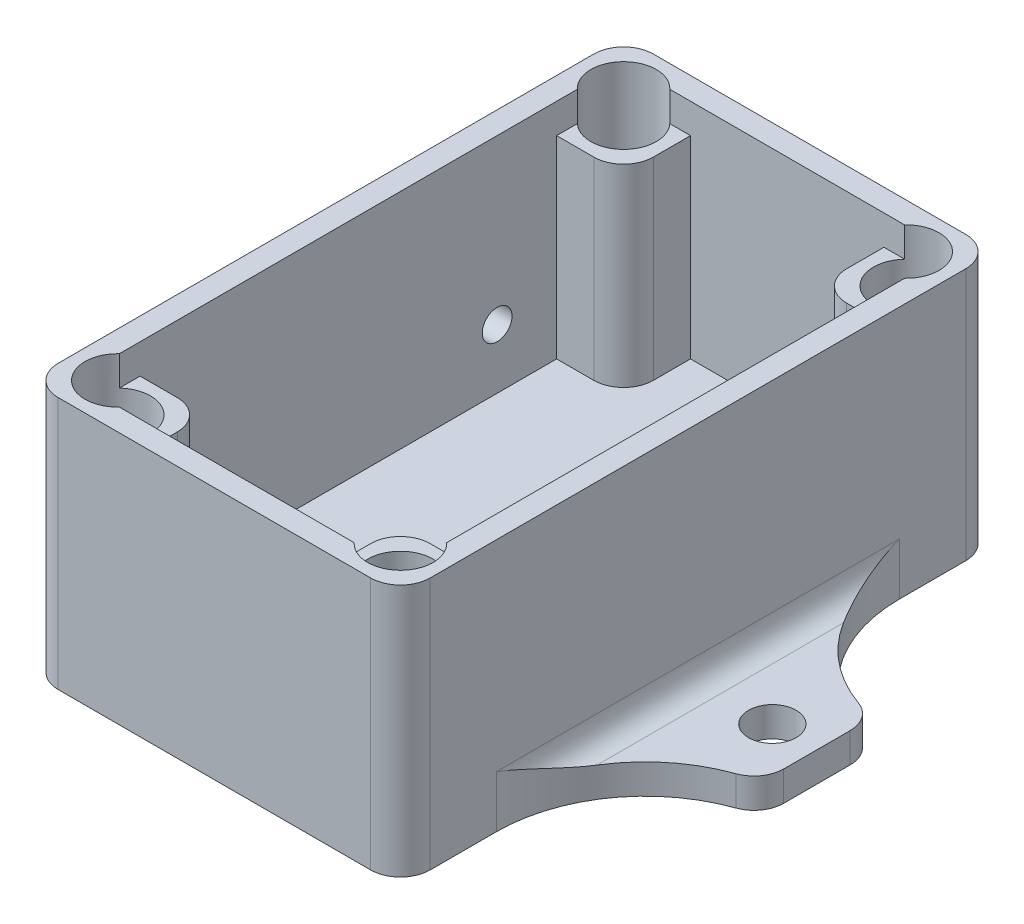
SolidWorks part; units mm, degrees
material "ABS"
ref_plane "Plan de face" through (0, 0, 0) normal (0, 0, 1) x (1, 0, 0)
ref_plane "Plan de dessus" through (0, 0, 0) normal (0, 1, 0) x (1, 0, 0)
ref_plane "Plan de droite" through (0, 0, 0) normal (1, 0, 0) x (0, 0, -1)
sketch "Esquisse1" plane through (0, 0, 0) normal (0, 1, 0) x (1, 0, 0)
  line L1 (-10.5, 20) -> (10.5, 20)
  line L2 (-12.5, 18) -> (-12.5, -18)
  line L3 (-10.5, -20) -> (10.5, -20)
  line L4 (12.5, 18) -> (12.5, -18)
  line L5 (-12.5, 20) -> (12.5, -20) construction
  line L6 (-12.5, -20) -> (12.5, 20) construction
  arc A0 (-12.5, -18) -> (-10.5, -20) centre (-10.5, -18) ccw
  arc A1 (10.5, -20) -> (12.5, -18) centre (10.5, -18) ccw
  arc A2 (10.5, 20) -> (12.5, 18) centre (10.5, 18) cw
  arc A3 (-10.5, 20) -> (-12.5, 18) centre (-10.5, 18) ccw
  point P0 (0, 0)
  dimension "D3" = 2
  dimension "D1" = 25
  dimension "D2" = 40
extrude "Base" add sketch "Esquisse1" along normal blind 2
sketch "Esquisse2" plane through (0, 2, 0) normal (0, 1, 0) x (1, 0, 0)
  line L9 (-10.5, -18.5) -> (10.5, -18.5)
  line L10 (11, -18) -> (11, 18)
  line L11 (10.5, 18.5) -> (-10.5, 18.5)
  line L12 (-11, 18) -> (-11, -18)
  line L13 (-10.5, -18.5) -> (10.5, -18.5)
  line L14 (11, -18) -> (11, 18)
  line L15 (10.5, 18.5) -> (-10.5, 18.5)
  line L16 (-11, 18) -> (-11, -18)
  arc A8 (-11, -18) -> (-10.5, -18.5) centre (-10.5, -18) ccw
  arc A9 (10.5, -18.5) -> (11, -18) centre (10.5, -18) ccw
  arc A10 (11, 18) -> (10.5, 18.5) centre (10.5, 18) ccw
  arc A11 (-10.5, 18.5) -> (-11, 18) centre (-10.5, 18) ccw
  arc A12 (-11, -18) -> (-10.5, -18.5) centre (-10.5, -18) ccw
  arc A13 (10.5, -18.5) -> (11, -18) centre (10.5, -18) ccw
  arc A14 (11, 18) -> (10.5, 18.5) centre (10.5, 18) ccw
  arc A15 (-10.5, 18.5) -> (-11, 18) centre (-10.5, 18) ccw
  arc M9 (-12.5, -18) -> (-10.5, -20) centre (-10.5, -18) ccw
  line M10 (-10.5, -20) -> (10.5, -20)
  arc M11 (10.5, -20) -> (12.5, -18) centre (10.5, -18) ccw
  line M12 (12.5, -18) -> (12.5, 18)
  arc M13 (12.5, 18) -> (10.5, 20) centre (10.5, 18) ccw
  line M14 (10.5, 20) -> (-10.5, 20)
  arc M15 (-10.5, 20) -> (-12.5, 18) centre (-10.5, 18) ccw
  line M16 (-12.5, 18) -> (-12.5, -18)
  dimension "D1" = 1.5
extrude "Mur" add sketch "Esquisse2" along normal blind 15 contours A15 L15 A14 L14 A13 L13 A12 L16 M16 M9 M10 M11 M12 M13 M14 M15 region at (-12.0283, 2, 0)
sketch "Esquisse3" plane through (0, 2, 0) normal (0, 1, 0) x (1, 0, 0)
  line L1 (-11, 18.5) -> (-6.5, 18.5)
  line L2 (-11, 18.5) -> (-11, 14)
  line L3 (-11, 14) -> (-6.5, 14)
  line L4 (-6.5, 18.5) -> (-6.5, 14)
  line L5 (10.5, 18.5) -> (-10.5, 18.5) construction
  line L6 (-11, 18) -> (-11, -18) construction
  line L7 (0, -55) -> (0, 55) construction
  line L8 (11, 14) -> (6.5, 14)
  line L9 (6.5, 18.5) -> (6.5, 14)
  line L10 (11, 18.5) -> (6.5, 18.5)
  line L11 (11, 18.5) -> (11, 14)
  line L12 (-55, 0) -> (55, 0) construction
  line L13 (11, -18.5) -> (11, -14)
  line L14 (11, -18.5) -> (6.5, -18.5)
  line L15 (6.5, -18.5) -> (6.5, -14)
  line L16 (11, -14) -> (6.5, -14)
  line L17 (-11, -14) -> (-6.5, -14)
  line L18 (-6.5, -18.5) -> (-6.5, -14)
  line L19 (-11, -18.5) -> (-6.5, -18.5)
  line L20 (-11, -18.5) -> (-11, -14)
  dimension "D1" = 4.5
extrude "Fixation Vis" add sketch "Esquisse3" along normal blind 13
sketch "Esquisse4" plane through (0, 15, 0) normal (0, 1, 0) x (1, 0, 0)
  line L8 (10.5, 20) -> (-10.5, 20) construction
  line L9 (-6.5, 14) -> (-12.5, 14) construction
  line L10 (-6.5, 14) -> (-6.5, 20) construction
  line L11 (-6.5, 20) -> (-12.5, 20) construction
  line L12 (-12.5, 14) -> (-12.5, 20) construction
  line L13 (-12.5, 18) -> (-12.5, -18) construction
  line L14 (0, -55) -> (0, 55) construction
  line L15 (-55, 0) -> (55, 0) construction
  circle A0 centre (-9.5, 17) radius 2.2
  circle A1 centre (9.5, 17) radius 2.2
  circle A2 centre (9.5, -17) radius 2.2
  circle A3 centre (-9.5, -17) radius 2.2
  point P21 (-9.5, 20)
  point P24 (-12.5, 17)
  dimension "D1" = 4.4
fillet "Congé1" radius 2 4 edges at (-6.5, 8.5, 14) (6.5, 8.5, 14) (6.5, 8.5, -14) (-6.5, 8.5, -14)
extrude "Insert M3" cut sketch "Esquisse4" against normal blind 6 and the other way up to next
sketch "Esquisse5" plane through (-12.5, 0, 0) normal (-1, 0, 0) x (0, 0, 1)
  line L0 (-18, 0) -> (18, 0) construction
  line L1 (-18, 17) -> (-18, 0) construction
  circle A0 centre (-10, 6) radius 1
  dimension "D1" = 2
  dimension "D2" = 6
  dimension "D3" = 8
extrude "Passe-Cable" cut sketch "Esquisse5" against normal up to next
sketch "Esquisse8" plane through (0, 0, 0) normal (0, 1, 0) x (1, 0, 0)
  line L0 (12.5, -18) -> (12.5, 18) construction
  line L1 (12.5, 3.75) -> (20.5, 3.75)
  line L2 (12.5, 3.75) -> (12.5, -3.75)
  line L3 (12.5, -3.75) -> (20.5, -3.75)
  line L4 (20.5, 3.75) -> (20.5, -3.75)
  line L5 (-12.5, 18) -> (-12.5, -18) construction
  line L6 (-12.5, -3.75) -> (-20.5, -3.75)
  line L7 (-12.5, -3.75) -> (-12.5, 3.75)
  line L8 (-12.5, 3.75) -> (-20.5, 3.75)
  line L9 (-20.5, -3.75) -> (-20.5, 3.75)
  point P12 (-20.5, 0)
  point P14 (20.5, 0)
  dimension "D1" = 8
  dimension "D2" = 7.5
extrude "Pates fixation" add sketch "Esquisse8" along normal blind 2
sketch "Esquisse9" plane through (0, 2, 0) normal (0, 1, 0) x (1, 0, 0)
  circle A0 centre (-17.5, 0) radius 1.6
  circle A1 centre (17.5, 0) radius 1.6
  dimension "D2" = 3.2
  dimension "D1" = 35
  dimension "D3" = 17.5
extrude "Passage_Vis" cut sketch "Esquisse9" against normal up to next
fillet "Congé_10mm" radius 10 4 edges at (12.5, 1, 3.75) (12.5, 1, -3.75) (-12.5, 1, -3.75) (-12.5, 1, 3.75)
fillet "Congé_2mm" radius 2 4 edges at (20.5, 1, -3.75) (20.5, 1, 3.75) (-20.5, 1, -3.75) (-20.5, 1, 3.75)
fillet "Congé_1,5mm" radius 1.5 2 edges at (-12.5, 2, 0) (12.5, 2, 0)
equation "\"D3@Esquisse9\"=\"D1@Esquisse9\"/2"
